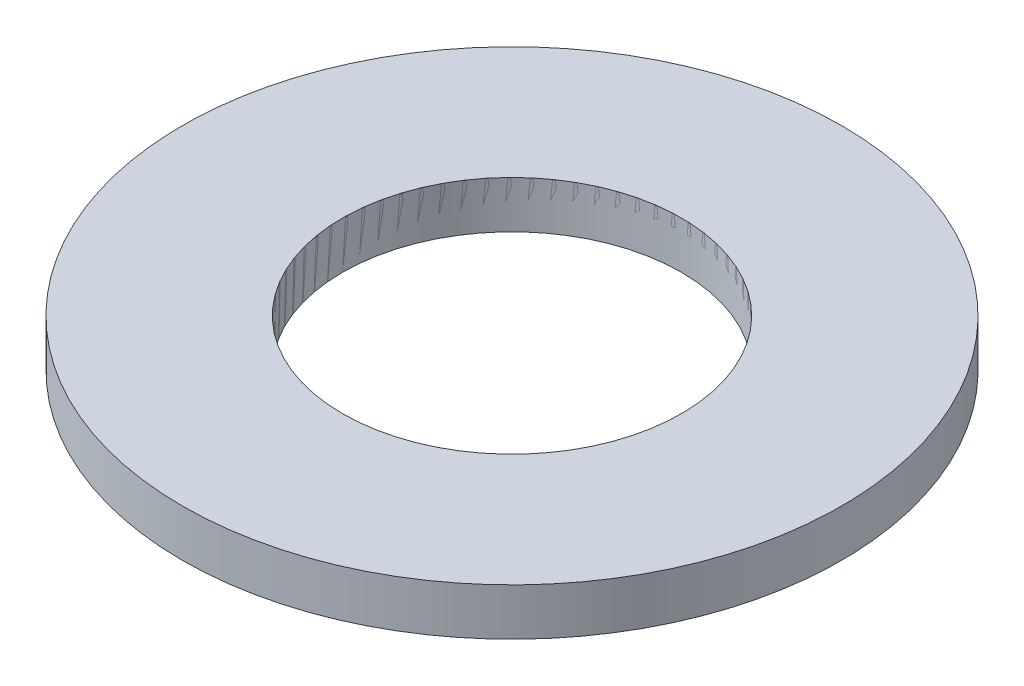
SolidWorks part; units mm, degrees
material "1345 Alloy"
ref_plane "Front Plane" through (0, 0, 0) normal (0, 0, 1) x (1, 0, 0)
ref_plane "Top Plane" through (0, 0, 0) normal (0, 1, 0) x (1, 0, 0)
ref_plane "Right Plane" through (0, 0, 0) normal (1, 0, 0) x (0, 0, -1)
sketch "Sketch1" plane through (0, 0, 0) normal (0, 1, 0) x (1, 0, 0)
  circle A0 centre (0, 0) radius 1750
extrude "Boss-Extrude1" add sketch "Sketch1" along normal blind 500
sketch "Sketch2" plane through (0, 500, 0) normal (0, 1, 0) x (1, 0, 0)
  circle A0 centre (0, 0) radius 900
extrude "Cut-Extrude2" cut sketch "Sketch2" against normal blind 300
sketch "Sketch3" plane through (0, 0, 0) normal (0, -1, 0) x (1, 0, 0)
  circle A0 centre (0, 0) radius 600
extrude "Cut-Extrude3" cut sketch "Sketch3" against normal blind 300
sketch "Sketch4" plane through (0, 0, 0) normal (0, -1, 0) x (-1, 0, 0)
  circle A0 centre (0, 0) radius 900.75
  circle A1 centre (0, 0) radius 1748.5
extrude "Cut-Extrude5" cut sketch "Sketch4" against normal blind 497
sketch "Sketch5" plane through (0, 0, 0) normal (0, 0, 1) x (1, 0, 0)
  line L0 (0, 0) -> (0, 250)
  line L1 (0, 250) -> (1750, 250)
  line L2 (1750, 0) -> (1750, 500) construction
  line L3 (1750, 250) -> (1750, 0)
  line L4 (1750, 0) -> (-1750, 0)
  line L5 (-1750, 0) -> (-1750, 250)
  line L6 (-1750, 500) -> (-1750, 0) construction
  line L7 (-1750, 250) -> (0, 250)
extrude "Cut-Extrude6" cut sketch "Sketch5" against normal through all both and the other way through all contours L7 L5 L4 L0 | L4 L3 L1 L0 region at (-875, 125, 0) region at (875, 125, 0)
